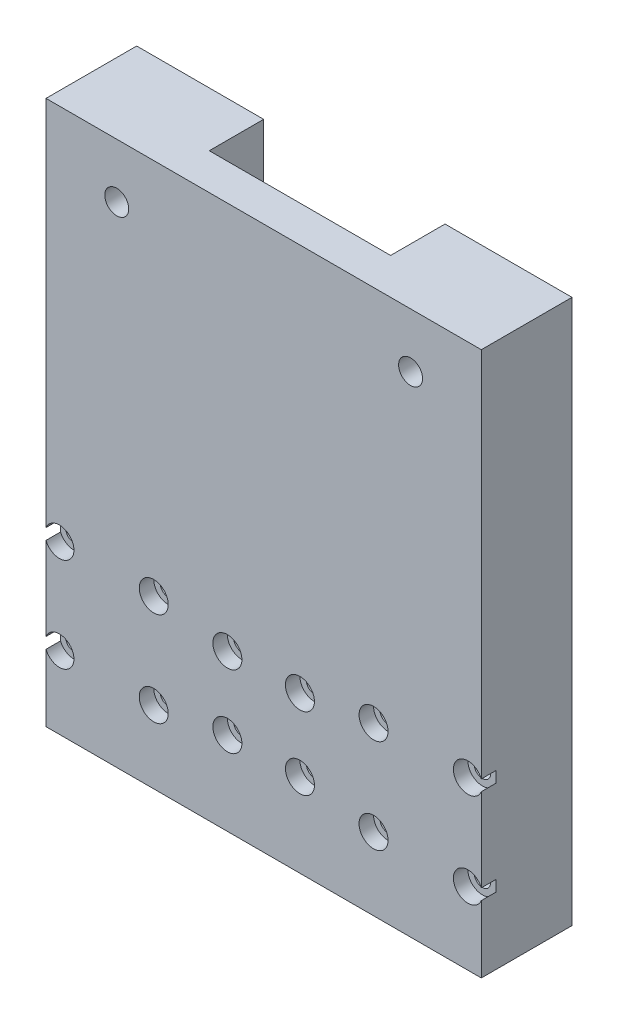
SolidWorks part; units mm, degrees
ref_plane "Front Plane" through (0, 0, 0) normal (0, 0, 1) x (1, 0, 0)
ref_plane "Top Plane" through (0, 0, 0) normal (0, 1, 0) x (1, 0, 0)
ref_plane "Right Plane" through (0, 0, 0) normal (1, 0, 0) x (0, 0, -1)
sketch "Sketch1" plane through (0, 0, 0) normal (0, 0, 1) x (1, 0, 0)
  line L1 (0, 0) -> (120, 0)
  line L2 (0, 0) -> (0, 150)
  line L3 (0, 150) -> (120, 150)
  line L4 (120, 0) -> (120, 150)
  dimension "D1" = 120
  dimension "D2" = 150
extrude "Boss-Extrude1" add sketch "Sketch1" along normal blind 25
sketch "Sketch2" plane through (0, 0, 25) normal (0, 0, 1) x (1, 0, 0)
  line L0 (60, 150) -> (60, 0) construction
  line L1 (120, 150) -> (0, 150) construction
  line L2 (0, 0) -> (120, 0) construction
  line L3 (0, 33) -> (120, 33) construction
  line L4 (0, 150) -> (0, 0) construction
  line L5 (120, 0) -> (120, 150) construction
  point P6 (29.7, 20)
  point P7 (29.7, 46)
  point P8 (3.7, 20)
  point P9 (3.7, 46)
  point P10 (116.3, 46)
  point P11 (116.3, 20)
  point P12 (90.3, 46)
  point P13 (90.3, 20)
  point P20 (50, 43)
  point P21 (70, 43)
  point P22 (70, 23)
  point P23 (50, 23)
  dimension "D1" = 30.3
  dimension "D2" = 26
  dimension "D3" = 26
  dimension "D4" = 20
  dimension "D5" = 13
  dimension "D6" = 10
  dimension "D7" = 10
hole_wizard "CBORE for M4 SHCS1" positions "3DSketch1" profile "Sketch3" counterbore size "M4" standard "ANSI Metric" end condition through all
sketch3d "3DSketch1"
  point P0 (3.7, 46, 25)
  point P3 (29.7, 46, 25)
  point P6 (3.7, 20, 25)
  point P9 (29.7, 20, 25)
  point P12 (90.3, 46, 25)
  point P15 (116.3, 46, 25)
  point P18 (116.3, 20, 25)
  point P21 (90.3, 20, 25)
  point P24 (50, 43, 25)
  point P27 (70, 43, 25)
  point P30 (70, 23, 25)
  point P33 (50, 23, 25)
sketch "Sketch3" plane through (3.7, 46, 25) normal (1, 0, 0) x (0, -1, 0)
  line L0 (0, 0) -> (0, 25)
  line L1 (0, 25) -> (2.25, 25)
  line L3 (2.25, 25) -> (2.25, 4)
  line L4 (2.25, 4) -> (4, 4)
  line L5 (4, 4) -> (4, 0)
  line L7 (4, 0) -> (0, 0)
  line L11 (0, -6.35) -> (0, 107.95) construction
  dimension "Thru Hole Dia." = 4.5
  dimension "Thru Hole Depth" = 25
  dimension "C'Bore Dia." = 8
  dimension "C'Bore Depth" = 4
sketch "Sketch4" plane through (0, 150, 0) normal (0, 1, 0) x (1, 0, 0)
  line L0 (60, 0) -> (60, -20.062) construction
  line L1 (120, 0) -> (0, 0) construction
  line L2 (35, 0) -> (35, -15)
  line L3 (35, -15) -> (85, -15)
  line L4 (85, 0) -> (85, -15)
  line L5 (35, 0) -> (85, 0)
  point P8 (60, -15)
  dimension "D1" = 25
  dimension "D2" = 15
extrude "Cut-Extrude1" cut sketch "Sketch4" against normal through all
sketch "Sketch5" plane through (0, 0, 25) normal (0, 0, 1) x (1, 0, 0)
  line L0 (0, 135) -> (120, 135) construction
  line L1 (0, 150) -> (0, 47.5199) construction
  line L2 (120, 47.5199) -> (120, 150) construction
  line L3 (120, 150) -> (0, 150) construction
  line L4 (60, 150) -> (60, 0) construction
  line L5 (60, 150) -> (60, 0) construction
  point P8 (19.5, 135)
  point P15 (100.5, 135)
  dimension "D1" = 15
  dimension "D2" = 40.5
hole_wizard "M6 Clearance Hole1" positions "3DSketch2" profile "Sketch6" hole size "M6" standard "ISO" end condition through all
sketch3d "3DSketch2"
  point P0 (19.5, 135, 25)
  point P3 (100.5, 135, 25)
sketch "Sketch6" plane through (19.5, 135, 25) normal (1, 0, 0) x (0, -1, 0)
  line L0 (0, 0) -> (0, 25)
  line L1 (0, 25) -> (3.3, 25)
  line L2 (3.3, 25) -> (3.3, 0)
  line L5 (3.3, 0) -> (0, 0)
  line L11 (0, -6.35) -> (0, 107.95) construction
  dimension "Thru Hole Dia." = 6.6
  dimension "Thru Hole Depth" = 25
